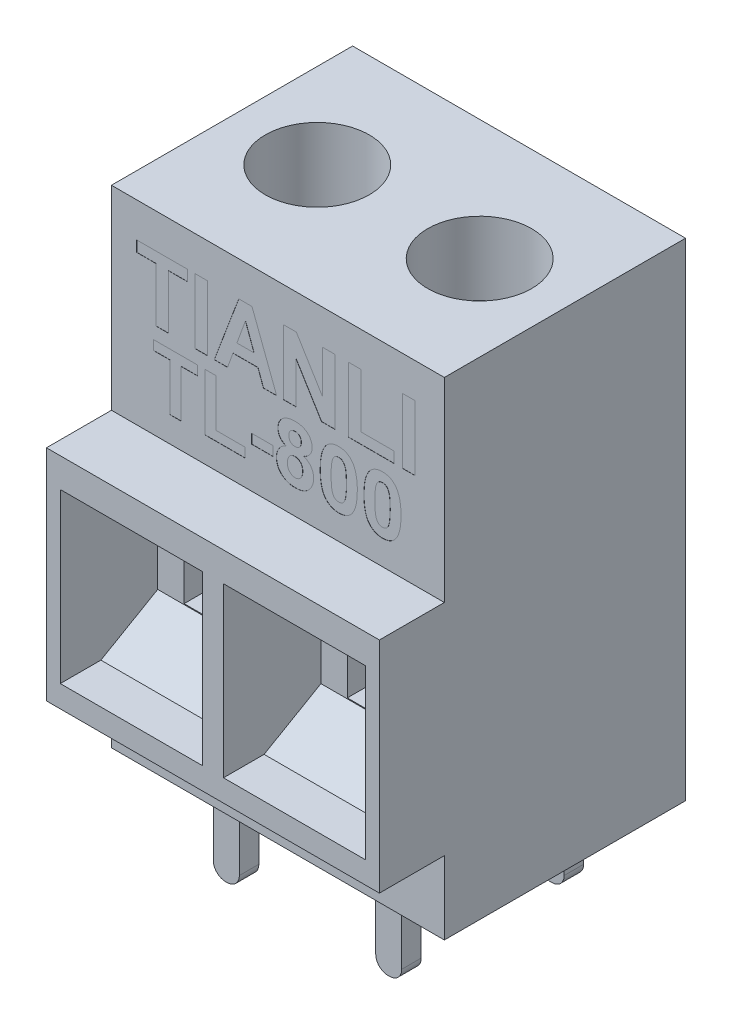
SolidWorks part; units mm, degrees
ref_plane "Front Plane" through (0, 0, 0) normal (0, 0, 1) x (1, 0, 0)
ref_plane "Top Plane" through (0, 0, 0) normal (0, 1, 0) x (1, 0, 0)
ref_plane "Right Plane" through (0, 0, 0) normal (1, 0, 0) x (0, 0, -1)
sketch "Sketch1" plane through (0, 0, 0) normal (1, 0, 0) x (0, 0, -1)
  line L0 (0, 66.3882) -> (0, -65.5147) construction
  line L1 (7.425, 15) -> (-7.425, 15)
  line L2 (-7.425, 15) -> (-7.425, 3)
  line L3 (-7.425, 3) -> (-11.425, 3)
  line L4 (-11.425, 3) -> (-11.425, -10.5)
  line L5 (-11.425, -10.5) -> (-7.425, -10.5)
  line L6 (-7.425, -10.5) -> (-7.425, -15)
  line L7 (-7.425, -15) -> (7.425, -15)
  line L8 (7.425, -15) -> (7.425, 15)
  point P15 (0, 15)
  point P16 (7.425, 0)
  dimension "D1" = 14.85
  dimension "D2" = 30
  dimension "D3" = 12
  dimension "D4" = 4
  dimension "D5" = 4.5
extrude "Boss-Extrude1" add sketch "Sketch1" along normal mid plane 20.5
sketch "Sketch2" plane through (0, 0, 11.425) normal (0, 0, 1) x (1, 0, 0)
  line L0 (0, 6.6704) -> (0, -3.1764) construction
  line L1 (9.4, -9.15) -> (0.65, -9.15)
  line L2 (-9.4, 1.2) -> (-0.65, 1.2)
  line L3 (-9.4, 1.2) -> (-9.4, -9.15)
  line L4 (-9.4, -9.15) -> (-0.65, -9.15)
  line L5 (-0.65, 1.2) -> (-0.65, -9.15)
  line L6 (-9.4, 1.2) -> (-0.65, -9.15) construction
  line L7 (-9.4, -9.15) -> (-0.65, 1.2) construction
  line L8 (0.65, 1.2) -> (0.65, -9.15)
  line L9 (9.4, 1.2) -> (0.65, 1.2)
  line L10 (9.4, 1.2) -> (9.4, -9.15)
  line L11 (10.25, -10.5) -> (-10.25, -10.5) construction
  point P3 (-5.025, -3.975)
  dimension "D1" = 8.75
  dimension "D2" = 10.35
  dimension "D3" = 1.35
  dimension "D4" = 1.3
extrude "Cut-Extrude1" cut sketch "Sketch2" against normal blind 6
sketch "Sketch4" plane through (0, 0, 5.425) normal (0, 0, 1) x (1, 0, 0)
  line L0 (-0.65, -9.15) -> (-0.65, 1.2) construction
  line L1 (-2.275, -0.875) -> (-7.775, -0.875)
  line L2 (-2.275, -0.875) -> (-2.275, -7.075)
  line L3 (-2.275, -7.075) -> (-7.775, -7.075)
  line L4 (-7.775, -0.875) -> (-7.775, -7.075)
  line L5 (-2.275, -0.875) -> (-7.775, -7.075) construction
  line L6 (-2.275, -7.075) -> (-7.775, -0.875) construction
  line L7 (-0.65, 1.2) -> (-9.4, 1.2) construction
  line L8 (0, 0) -> (0, 5.9557) construction
  line L9 (2.275, -7.075) -> (7.775, -7.075)
  line L10 (7.775, -0.875) -> (7.775, -7.075)
  line L11 (2.275, -0.875) -> (7.775, -0.875)
  line L12 (2.275, -0.875) -> (2.275, -7.075)
  point P0 (-5.025, -3.975)
  point P7 (-0.65, -3.975)
  point P10 (-5.025, 1.2)
  dimension "D1" = 6.2
  dimension "D2" = 5.5
extrude "Cut-Extrude2" cut sketch "Sketch4" against normal blind 6
chamfer "Chamfer1" distance 3.5 angle 30 4 edges at (5.025, -9.15, 5.425) (5.025, 1.2, 5.425) (-5.025, 1.2, 5.425) (-5.025, -9.15, 5.425) first distance on face at (5.025, -9.15, 8.425) first distance on face at (5.025, 1.2, 8.425) first distance on face at (-5.025, 1.2, 8.425) first distance on face at (-5.025, -9.15, 8.425)
sketch "Sketch5" plane through (0, 15, 0) normal (0, 1, 0) x (1, 0, 0)
  line L0 (0, 0) -> (-10.25, 0) construction
  line L1 (0, 0) -> (0, -7.425) construction
  line L2 (-10.25, 7.425) -> (-10.25, -7.425) construction
  line L3 (10.25, -7.425) -> (-10.25, -7.425) construction
  circle A0 centre (-5, 0) radius 3.2
  circle A1 centre (5, 0) radius 3.2
  dimension "D1" = 6.4
  dimension "D2" = 10
extrude "Cut-Extrude3" cut sketch "Sketch5" against normal blind 4.5
sketch "Sketch6" plane through (0, 10.5, 0) normal (0, 1, 0) x (1, 0, 0)
  line L0 (-7.2223, 0) -> (-2.7777, 0)
  line L1 (-5, -1.75) -> (-5, 1.75)
  line L2 (0, 0) -> (0, -2.7983) construction
  line L3 (5, -1.75) -> (5, 1.75)
  line L4 (7.2223, 0) -> (2.7777, 0)
  line L5 (-5, 3.2) -> (-5, -3.2) construction
  circle A2 centre (-5, 0) radius 3.2 construction
  circle A3 centre (-5, 0) radius 3.2 construction
  point P10 (-5, 0)
  dimension "D1" = 3.5
  dimension "D2" = 5
extrude "Cut-Extrude-Thin1" cut sketch "Sketch6" against normal blind 1.5 thin thin type mid plane wall 1
sketch "Sketch7" plane through (0, -15, 0) normal (0, -1, 0) x (1, 0, 0)
  line L0 (0, 14.2864) -> (0, -10.6744) construction
  line L1 (-13.0408, 0) -> (12.0493, 0) construction
  line L2 (-4.2, 4.4) -> (-5.8, 4.4)
  line L3 (4.2, 5.6) -> (5.8, 5.6)
  line L4 (4.2, 5.6) -> (4.2, 4.4)
  line L5 (4.2, 4.4) -> (5.8, 4.4)
  line L6 (5.8, 5.6) -> (5.8, 4.4)
  line L7 (4.2, 5.6) -> (5.8, 4.4) construction
  line L8 (4.2, 4.4) -> (5.8, 5.6) construction
  line L9 (-5.8, 5.6) -> (-5.8, 4.4)
  line L10 (-4.2, 5.6) -> (-5.8, 5.6)
  line L11 (-4.2, 5.6) -> (-4.2, 4.4)
  line L12 (-4.2, -5.6) -> (-4.2, -4.4)
  line L13 (-4.2, -5.6) -> (-5.8, -5.6)
  line L14 (-5.8, -5.6) -> (-5.8, -4.4)
  line L15 (-4.2, -4.4) -> (-5.8, -4.4)
  line L16 (4.2, -4.4) -> (5.8, -4.4)
  line L17 (5.8, -5.6) -> (5.8, -4.4)
  line L18 (4.2, -5.6) -> (5.8, -5.6)
  line L19 (4.2, -5.6) -> (4.2, -4.4)
  point P9 (5, 5)
  dimension "D1" = 10
  dimension "D2" = 10
  dimension "D3" = 1.6
  dimension "D4" = 1.2
extrude "Boss-Extrude2" add sketch "Sketch7" along normal blind 5.45
fillet "Fillet1" radius 0.75 8 edges at (4.2, -20.45, -5) (5.8, -20.45, -5) (-4.2, -20.45, -5) (-5.8, -20.45, -5) (-5.8, -20.45, 5) (-4.2, -20.45, 5) (4.2, -20.45, 5) (5.8, -20.45, 5)
sketch "Sketch8" plane through (0, 0, 7.425) normal (0, 0, 1) x (1, 0, 0)
  line L0 (-10.25, 8.8613) -> (10.25, 8.8613) construction
  line L1 (-10.25, 4.5647) -> (10.25, 4.5647) construction
  line L2 (10.25, 15) -> (10.25, 3) construction
  text T0 "TIANLI" font "Arial" height 4
  text T1 "TL-800" font "Arial" height 3.5
  point P4 (0, 8.8613)
  point P5 (0, 4.5647)
extrude "Cut-Extrude4" cut sketch "Sketch8" against normal blind 0.01
